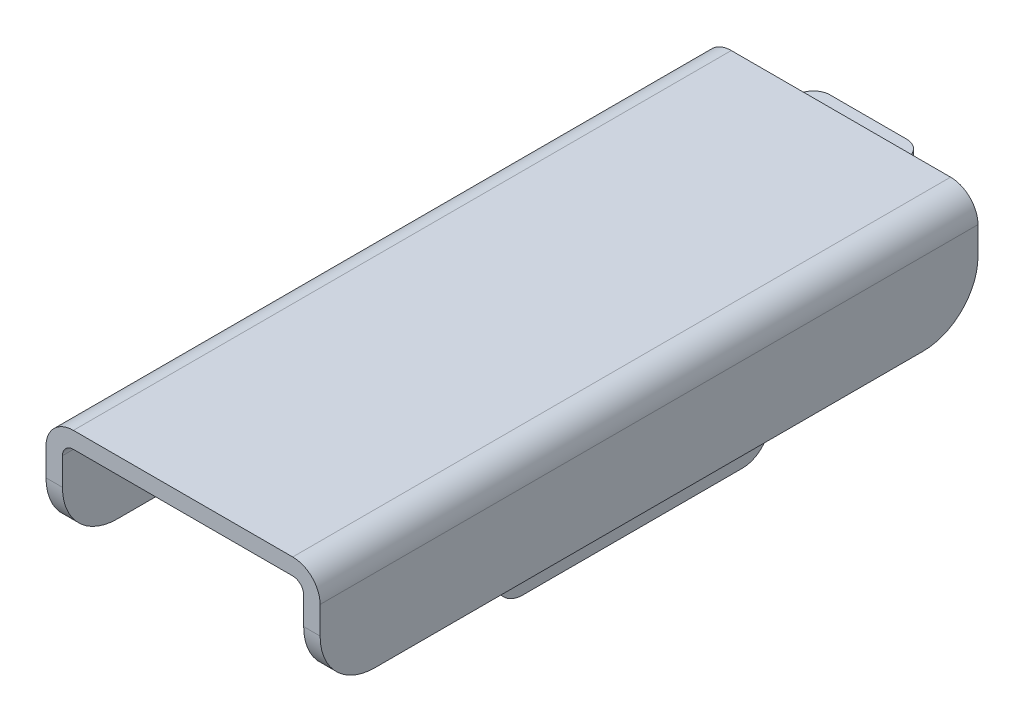
SolidWorks part; units mm, degrees
ref_plane "Front Plane" through (0, 0, 0) normal (0, 0, 1) x (1, 0, 0)
ref_plane "Top Plane" through (0, 0, 0) normal (0, 1, 0) x (1, 0, 0)
ref_plane "Right Plane" through (0, 0, 0) normal (1, 0, 0) x (0, 0, -1)
sketch "Sketch1" plane through (0, 0, 0) normal (0, 0, 1) x (1, 0, 0)
  line L16 (-48.5859, 38.4719) -> (-88.5859, 38.4719)
  line L17 (-93.5859, 33.4719) -> (-93.5859, 18.4719)
  line L18 (-93.5859, 18.4719) -> (-90.5859, 18.4719)
  line L19 (-90.5859, 18.4719) -> (-90.5859, 33.4719)
  line L20 (-88.5859, 35.4719) -> (-48.5859, 35.4719)
  line L21 (-46.5859, 33.4719) -> (-46.5859, 18.4719)
  line L22 (-46.5859, 18.4719) -> (-43.5859, 18.4719)
  line L23 (-43.5859, 18.4719) -> (-43.5859, 33.4719)
  arc A8 (-88.5859, 38.4719) -> (-93.5859, 33.4719) centre (-88.5859, 33.4719) ccw
  arc A9 (-88.5859, 35.4719) -> (-90.5859, 33.4719) centre (-88.5859, 33.4719) ccw
  arc A10 (-46.5859, 33.4719) -> (-48.5859, 35.4719) centre (-48.5859, 33.4719) ccw
  arc A11 (-43.5859, 33.4719) -> (-48.5859, 38.4719) centre (-48.5859, 33.4719) ccw
extrude "Boss-Extrude1" add sketch "Sketch1" along normal blind 120
fillet "Fillet1" radius 10 4 edges at (-92.0859, 18.4719, 0) (-45.0859, 18.4719, 0) (-92.0859, 18.4719, 120) (-45.0859, 18.4719, 120)
sketch "Sketch2" plane through (0, 18.4719, 0) normal (0, -1, 0) x (1, 0, 0)
  line L0 (-46.5859, 110) -> (-46.5859, 10) construction
  line L1 (-46.5859, 35) -> (-49.5859, 35)
  line L2 (-46.5859, 35) -> (-46.5859, 85)
  line L3 (-46.5859, 85) -> (-49.5859, 85)
  line L4 (-49.5859, 35) -> (-49.5859, 85)
  line L5 (-43.5859, 60) -> (-93.5859, 60) construction
  line L6 (-43.5859, 110) -> (-43.5859, 10) construction
  line L7 (-93.5859, 110) -> (-93.5859, 10) construction
  line L8 (-68.5859, 60) -> (-68.5859, 40.7332) construction
  line L9 (-87.5859, 35) -> (-87.5859, 85)
  line L10 (-90.5859, 85) -> (-87.5859, 85)
  line L11 (-90.5859, 35) -> (-90.5859, 85)
  line L12 (-90.5859, 35) -> (-87.5859, 35)
extrude "Boss-Extrude2" add sketch "Sketch2" against normal up to surface (17 mm away) and the other way blind 5 up to face at (-68.5859, 35.4719, 60)
sketch "Sketch3" plane through (0, 35.4719, 0) normal (0, -1, 0) x (1, 0, 0)
  line L0 (-68.5859, 0) -> (-68.5859, 20.5264) construction
  line L1 (-58.5859, 10) -> (-78.5859, 10)
  line L2 (-58.5859, 10) -> (-58.5859, -5)
  line L3 (-58.5859, -5) -> (-78.5859, -5)
  line L4 (-78.5859, 10) -> (-78.5859, -5)
  line L5 (-88.5859, 0) -> (-48.5859, 0) construction
  dimension "D1" = 10
  dimension "D2" = 20
  dimension "D3" = 15
  dimension "D4" = 10
extrude "Boss-Extrude3" add sketch "Sketch3" along normal blind 3
fillet "Fillet2" radius 5 4 edges at (-89.0859, 13.4719, 35) (-89.0859, 13.4719, 85) (-48.0859, 13.4719, 35) (-48.0859, 13.4719, 85)
chamfer "Chamfer1" distance 4 angle 45 1 edges at (-68.5859, 35.4719, 10)
fillet "Fillet3" radius 4 2 edges at (-68.5859, 35.4719, 14) (-68.5859, 32.4719, 11)
fillet "Fillet4" radius 3 2 edges at (-78.5859, 33.9719, -5) (-58.5859, 33.9719, -5)
sketch "Sketch4" plane through (0, 35.4719, 0) normal (0, -1, 0) x (1, 0, 0)
  line L0 (-46.5859, 35) -> (-46.5859, 10) construction
  line L1 (-46.5859, 20) -> (-90.5859, 20)
  line L2 (-46.5859, 20) -> (-46.5859, 23)
  line L3 (-46.5859, 23) -> (-90.5859, 23)
  line L4 (-90.5859, 20) -> (-90.5859, 23)
  line L5 (-90.5859, 35) -> (-90.5859, 10) construction
  line L6 (-46.5859, 110) -> (-46.5859, 85) construction
  line L7 (-46.5859, 100) -> (-90.5859, 100)
  line L8 (-46.5859, 100) -> (-46.5859, 97)
  line L9 (-46.5859, 97) -> (-90.5859, 97)
  line L10 (-90.5859, 100) -> (-90.5859, 97)
  line L11 (-90.5859, 110) -> (-90.5859, 85) construction
  line L12 (-88.5859, 120) -> (-48.5859, 120) construction
  line L13 (-88.5859, 0) -> (-78.5859, 0) construction
  line L14 (-68.5859, 97) -> (-68.5859, 23) construction
  dimension "D1" = 3
  dimension "D2" = 20
  dimension "D3" = 3
  dimension "D4" = 20
extrude "Boss-Extrude4" add sketch "Sketch4" along normal blind 5
fillet "Fillet5" radius 3 2 edges at (-49.5859, 35.4719, 60) (-87.5859, 35.4719, 60)
sketch "Sketch11" plane through (0, 35.4719, 0) normal (0, -1, 0) x (1, 0, 0)
  line L1 (-60.5859, 108) -> (-76.5859, 108)
  line L2 (-60.5859, 108) -> (-60.5859, 118)
  line L3 (-60.5859, 118) -> (-76.5859, 118)
  line L4 (-76.5859, 108) -> (-76.5859, 118)
extrude "Cut-Extrude9" cut sketch "Sketch11" against normal blind 2
